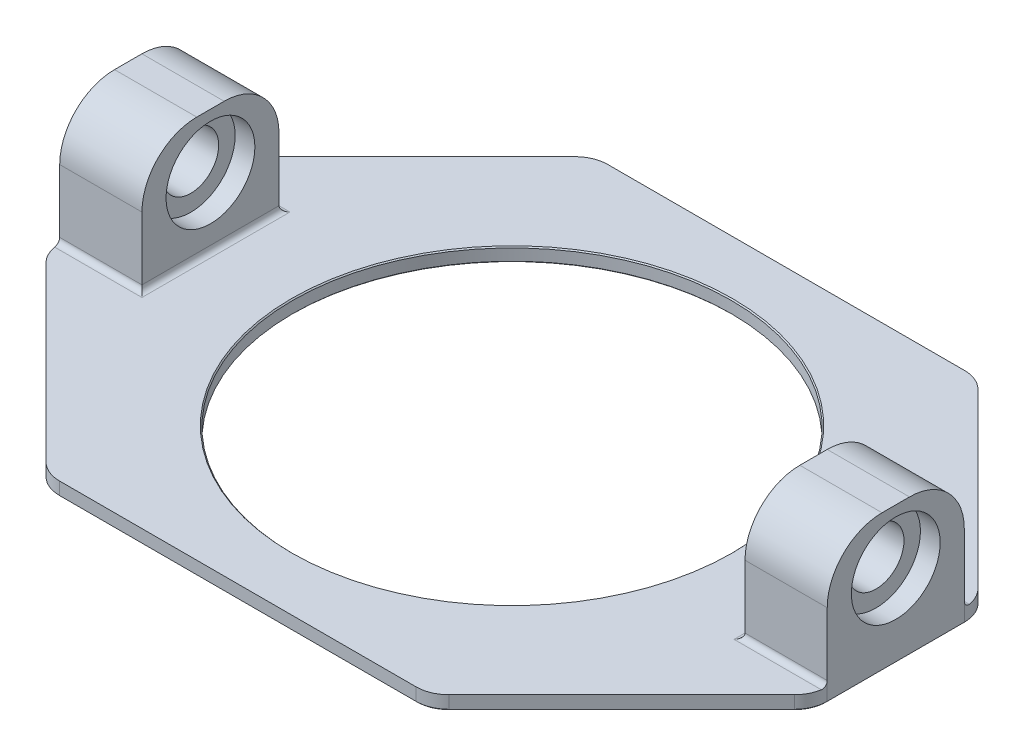
SolidWorks part; units mm, degrees
ref_plane "前视基准面" through (0, 0, 0) normal (0, 0, 1) x (1, 0, 0)
ref_plane "上视基准面" through (0, 0, 0) normal (0, 1, 0) x (1, 0, 0)
ref_plane "右视基准面" through (0, 0, 0) normal (1, 0, 0) x (0, 0, -1)
other "Configuration Table"
sketch "草图1" plane through (0, 0, 0) normal (0, 1, 0) x (1, 0, 0)
  line L1 (0, 0) -> (280, 0)
  line L2 (0, 0) -> (0, -280)
  line L3 (0, -280) -> (280, -280)
  line L4 (280, 0) -> (280, -280)
  dimension "D1" = 280
  dimension "D2" = 280
extrude "凸台-拉伸1" add sketch "草图1" along normal blind 5
sketch "草图2" plane through (0, 5, 0) normal (0, 1, 0) x (1, 0, 0)
  line L0 (0, -280) -> (280, -280) construction
  circle A0 centre (140, -180) radius 80
  point P4 (140, -280)
  point P7 (235.17, -280)
  dimension "D1" = 160
  dimension "D2" = 0
  dimension "D3" = 100
extrude "切除-拉伸1" cut sketch "草图2" against normal blind 5
sketch "草图3" plane through (0, 5, 0) normal (0, 1, 0) x (1, 0, 0)
  line L0 (0, 0) -> (0, -280) construction
  line L1 (0, -155) -> (30, -155)
  line L2 (0, -155) -> (0, -205)
  line L3 (0, -205) -> (30, -205)
  line L4 (30, -155) -> (30, -205)
  line L5 (280, -280) -> (280, 0) construction
  line L6 (280, -155) -> (250, -155)
  line L7 (280, -155) -> (280, -205)
  line L8 (280, -205) -> (250, -205)
  line L9 (250, -155) -> (250, -205)
  circle A0 centre (140, -180) radius 80 construction
  point P12 (30, -180)
  point P15 (250, -180)
  dimension "D1" = 0
  dimension "D2" = 0
  dimension "D3" = 50
  dimension "D4" = 50
  dimension "D5" = 30
  dimension "D6" = 30
extrude "凸台-拉伸2" add sketch "草图3" along normal blind 45
sketch "草图4" plane through (280, 0, 0) normal (1, 0, 0) x (0, 0, -1)
  line L0 (-205, 50) -> (-155, 50) construction
  circle A0 centre (-180, 30) radius 10.2
  point P4 (-180, 50)
  dimension "D1" = 0
  dimension "12.5" = 20.4
  dimension "D2" = 20
extrude "切除-拉伸2" cut sketch "草图4" against normal through all
sketch "草图5" plane through (280, 0, 0) normal (1, 0, 0) x (0, 0, -1)
  circle A0 centre (-180, 30) radius 16.2
  dimension "D1" = 32.4
extrude "切除-拉伸3" cut sketch "草图5" against normal blind 7.2
sketch "草图6" plane through (250, 0, 0) normal (-1, 0, 0) x (0, 0, 1)
  circle A0 centre (180, 30) radius 16.2
  dimension "D1" = 32.4
extrude "切除-拉伸4" cut sketch "草图6" against normal blind 7.2
sketch "草图7" plane through (30, 0, 0) normal (1, 0, 0) x (0, 0, -1)
  circle A0 centre (-180, 30) radius 16.2
  dimension "D1" = 32.4
extrude "切除-拉伸5" cut sketch "草图7" against normal blind 7.2
sketch "草图8" plane through (0, 0, 0) normal (-1, 0, 0) x (0, 0, 1)
  circle A0 centre (180, 30) radius 16.2
  dimension "D1" = 32.4
extrude "切除-拉伸6" cut sketch "草图8" against normal blind 7.2
sketch "草图9" plane through (0, 5, 0) normal (0, 1, 0) x (1, 0, 0)
  line L0 (280, -155) -> (280, 0) construction
  line L1 (0, 0) -> (280, 0)
  line L2 (0, 0) -> (0, -80)
  line L3 (0, -80) -> (280, -80)
  line L4 (280, 0) -> (280, -80)
  circle A0 centre (140, -180) radius 80 construction
  dimension "D1" = 100
extrude "切除-拉伸7" cut sketch "草图9" against normal through all
chamfer "倒角1" distance 70 angle 45 4 edges at (280, 2.5, 80) (280, 2.5, 280) (0, 2.5, 280) (0, 2.5, 80)
fillet "圆角1" radius 20 4 edges at (265, 50, 205) (265, 50, 155) (15, 50, 205) (15, 50, 155)
fillet "圆角2" radius 12 8 edges at (70, 2.5, 80) (210, 2.5, 80) (280, 2.5, 150) (280, 2.5, 210) (210, 2.5, 280) (70, 2.5, 280) (0, 2.5, 210) (0, 2.5, 150)
chamfer "倒角2" distance 0.4 angle 45 1 edges at (140, 5, 260)
fillet "圆角3" radius 2 6 edges at (250, 5, 180) (265, 5, 205) (265, 5, 155) (15, 5, 155) (30, 5, 180) (15, 5, 205)
sketch "草图10" plane through (0, 0, 0) normal (0, -1, 0) x (-1, 0, 0)
  line L1 (-140, -80) -> (-140, -118.5005) construction
  line L3 (0, -154.9706) -> (0, -205.0294) construction
  line L4 (-74.9706, -80) -> (-205.0294, -80) construction
  circle A0 centre (-20, -187.5) radius 1.6
  circle A1 centre (-20, -172.5) radius 1.6
  circle A5 centre (-260, -187.5) radius 1.6
  circle A6 centre (-260, -172.5) radius 1.6
  circle A7 centre (-140, -180) radius 80 construction
  dimension "D1" = 3.2
  dimension "D2" = 3.2
  dimension "D4" = 20
  dimension "D5" = 15
  dimension "D6" = 7.5
  dimension "D3" = 20
extrude "切除-拉伸8" cut sketch "草图10" against normal blind 20
sketch "草图11" plane through (0, 0, 0) normal (0, -1, 0) x (-1, 0, 0)
  circle A4 centre (-20, -172.5) radius 2.35
  circle A5 centre (-20, -187.5) radius 2.35
  circle A6 centre (-260, -172.5) radius 2.35
  circle A7 centre (-260, -187.5) radius 2.35
  dimension "D1" = 4.7
  dimension "D2" = 4.7
  dimension "D3" = 4.7
  dimension "D4" = 4.7
extrude "切除-拉伸9" cut sketch "草图11" against normal blind 4.2
chamfer "倒角4" distance 0.4 angle 45 21 edges at (0.9134, 0, 150.3784) (0, 0, 180) (0.9134, 0, 209.6216) (35, 0, 245) (70.3784, 0, 279.0866) (140, 0, 280) (209.6216, 0, 279.0866) (245, 0, 245) (279.0866, 0, 209.6216) (280, 0, 180) (279.0866, 0, 150.3784) (245, 0, 115) (209.6216, 0, 80.9134) (140, 0, 80) (70.3784, 0, 80.9134) (35, 0, 115) (140, 0, 260) (20, 0, 170.15) (260, 0, 185.15) (260, 0, 170.15) (20, 0, 185.15)
